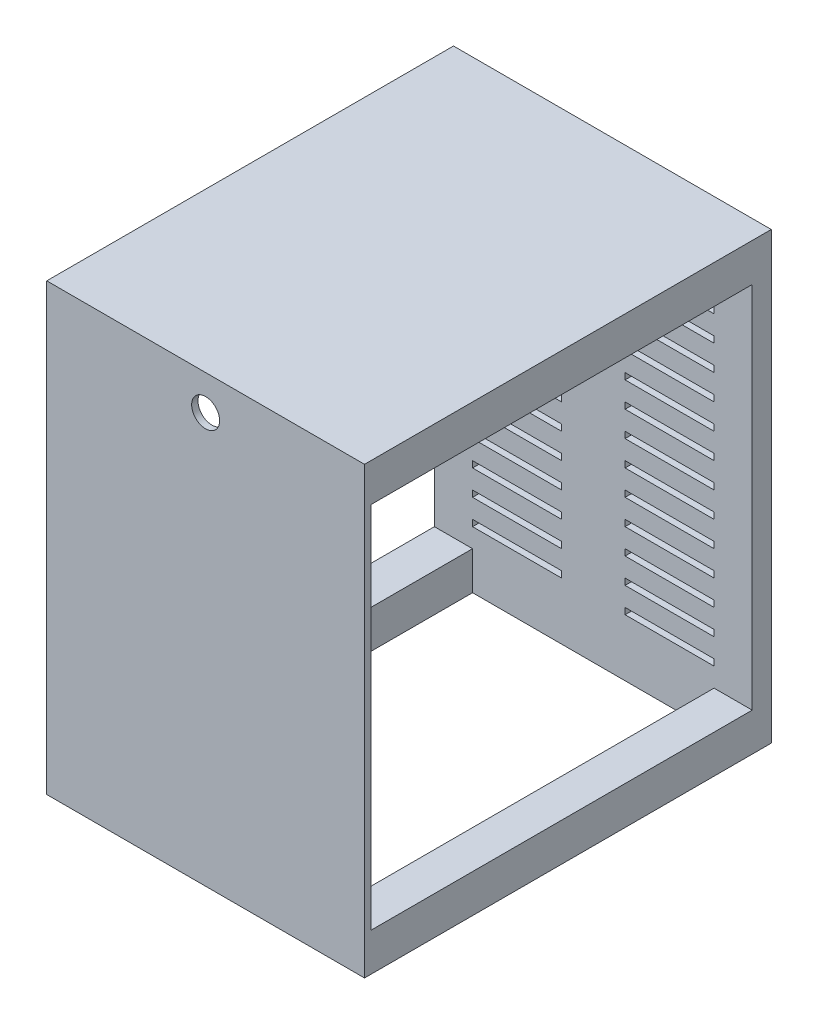
SolidWorks part; units mm, degrees
ref_plane "Alzado" through (0, 0, 0) normal (0, 0, 1) x (1, 0, 0)
ref_plane "Planta" through (0, 0, 0) normal (0, 1, 0) x (1, 0, 0)
ref_plane "Vista lateral" through (0, 0, 0) normal (1, 0, 0) x (0, 0, -1)
sketch "Croquis1" plane through (0, 0, 0) normal (0, 0, 1) x (1, 0, 0)
  line L1 (-125, -175) -> (125, -175)
  line L2 (-125, -175) -> (-125, 175)
  line L3 (-125, 175) -> (125, 175)
  line L4 (125, -175) -> (125, 175)
  line L5 (-125, -175) -> (125, 175) construction
  line L6 (-125, 175) -> (125, -175) construction
  point P0 (0, 0)
  dimension "D1" = 250
  dimension "D2" = 350
extrude "Saliente-Extruir2" add sketch "Croquis1" along normal blind 15 contours L3 L4 L1 L2
sketch "Croquis2" plane through (0, 0, 15) normal (0, 0, 1) x (1, 0, 0)
  line L1 (-125, 175) -> (-95, 175)
  line L2 (-125, 175) -> (-125, 145)
  line L3 (-125, 145) -> (-95, 145)
  line L4 (-95, 175) -> (-95, 145)
  line L5 (125, 175) -> (95, 175)
  line L6 (125, 175) -> (125, 145)
  line L7 (125, 145) -> (95, 145)
  line L8 (95, 175) -> (95, 145)
  line L9 (-125, -175) -> (-95, -175)
  line L10 (-125, -175) -> (-125, -145)
  line L11 (-125, -145) -> (-95, -145)
  line L12 (-95, -175) -> (-95, -145)
  line L13 (125, -175) -> (95, -175)
  line L14 (125, -175) -> (125, -145)
  line L15 (125, -145) -> (95, -145)
  line L16 (95, -175) -> (95, -145)
  dimension "D1" = 30
  dimension "D2" = 30
extrude "Saliente-Extruir3" add sketch "Croquis2" along normal blind 300
sketch "Croquis3" plane through (0, 0, 315) normal (0, 0, 1) x (1, 0, 0)
  line L1 (-125, 175) -> (125, 175)
  line L2 (-125, 175) -> (-125, -175)
  line L3 (-125, -175) -> (125, -175)
  line L4 (125, 175) -> (125, -175)
extrude "Saliente-Extruir4" add sketch "Croquis3" along normal blind 5
sketch "Croquis7" plane through (0, 0, 0) normal (0, 0, -1) x (-1, 0, 0)
  line L0 (25, 135) -> (95, 135)
  line L1 (-95, 135) -> (-25, 135)
  line L2 (-95, 135) -> (-95, 130)
  line L3 (-95, 130) -> (-25, 130)
  line L4 (-25, 135) -> (-25, 130)
  line L5 (95, 135) -> (95, 130)
  line L6 (25, 130) -> (95, 130)
  line L7 (25, 135) -> (25, 130)
  line L8 (25, 115) -> (95, 115)
  line L9 (95, 115) -> (95, 110)
  line L10 (25, 110) -> (95, 110)
  line L11 (25, 115) -> (25, 110)
  line L12 (25, 95) -> (95, 95)
  line L13 (95, 95) -> (95, 90)
  line L14 (25, 90) -> (95, 90)
  line L15 (25, 95) -> (25, 90)
  line L16 (25, 75) -> (95, 75)
  line L17 (95, 75) -> (95, 70)
  line L18 (25, 70) -> (95, 70)
  line L19 (25, 75) -> (25, 70)
  line L20 (25, 55) -> (95, 55)
  line L21 (95, 55) -> (95, 50)
  line L22 (25, 50) -> (95, 50)
  line L23 (25, 55) -> (25, 50)
  line L24 (25, 35) -> (95, 35)
  line L25 (95, 35) -> (95, 30)
  line L26 (25, 30) -> (95, 30)
  line L27 (25, 35) -> (25, 30)
  line L28 (25, 15) -> (95, 15)
  line L29 (95, 15) -> (95, 10)
  line L30 (25, 10) -> (95, 10)
  line L31 (25, 15) -> (25, 10)
  line L32 (25, -5) -> (95, -5)
  line L33 (95, -5) -> (95, -10)
  line L34 (25, -10) -> (95, -10)
  line L35 (25, -5) -> (25, -10)
  line L36 (25, -25) -> (95, -25)
  line L37 (95, -25) -> (95, -30)
  line L38 (25, -30) -> (95, -30)
  line L39 (25, -25) -> (25, -30)
  line L40 (25, -45) -> (95, -45)
  line L41 (95, -45) -> (95, -50)
  line L42 (25, -50) -> (95, -50)
  line L43 (25, -45) -> (25, -50)
  line L64 (-95, 115) -> (-25, 115)
  line L65 (-25, 115) -> (-25, 110)
  line L66 (-95, 110) -> (-25, 110)
  line L67 (-95, 115) -> (-95, 110)
  line L68 (-95, 95) -> (-25, 95)
  line L69 (-25, 95) -> (-25, 90)
  line L70 (-95, 90) -> (-25, 90)
  line L71 (-95, 95) -> (-95, 90)
  line L72 (-95, 75) -> (-25, 75)
  line L73 (-25, 75) -> (-25, 70)
  line L74 (-95, 70) -> (-25, 70)
  line L75 (-95, 75) -> (-95, 70)
  line L76 (-95, 55) -> (-25, 55)
  line L77 (-25, 55) -> (-25, 50)
  line L78 (-95, 50) -> (-25, 50)
  line L79 (-95, 55) -> (-95, 50)
  line L80 (-95, 35) -> (-25, 35)
  line L81 (-25, 35) -> (-25, 30)
  line L82 (-95, 30) -> (-25, 30)
  line L83 (-95, 35) -> (-95, 30)
  line L84 (-95, 15) -> (-25, 15)
  line L85 (-25, 15) -> (-25, 10)
  line L86 (-95, 10) -> (-25, 10)
  line L87 (-95, 15) -> (-95, 10)
  line L88 (-95, -5) -> (-25, -5)
  line L89 (-25, -5) -> (-25, -10)
  line L90 (-95, -10) -> (-25, -10)
  line L91 (-95, -5) -> (-95, -10)
  line L92 (-95, -25) -> (-25, -25)
  line L93 (-25, -25) -> (-25, -30)
  line L94 (-95, -30) -> (-25, -30)
  line L95 (-95, -25) -> (-95, -30)
  line L96 (-95, -45) -> (-25, -45)
  line L97 (-25, -45) -> (-25, -50)
  line L98 (-95, -50) -> (-25, -50)
  line L99 (-95, -45) -> (-95, -50)
  line L120 (-95, -65) -> (-25, -65)
  line L121 (-25, -65) -> (-25, -70)
  line L122 (-95, -70) -> (-25, -70)
  line L123 (-95, -65) -> (-95, -70)
  line L124 (25, -65) -> (95, -65)
  line L125 (95, -65) -> (95, -70)
  line L126 (25, -70) -> (95, -70)
  line L127 (25, -65) -> (25, -70)
  line L128 (-95, -85) -> (-25, -85)
  line L129 (-25, -85) -> (-25, -90)
  line L130 (-95, -90) -> (-25, -90)
  line L131 (-95, -85) -> (-95, -90)
  line L132 (25, -85) -> (95, -85)
  line L133 (95, -85) -> (95, -90)
  line L134 (25, -90) -> (95, -90)
  line L135 (25, -85) -> (25, -90)
  line L136 (-95, -105) -> (-25, -105)
  line L137 (-25, -105) -> (-25, -110)
  line L138 (-95, -110) -> (-25, -110)
  line L139 (-95, -105) -> (-95, -110)
  line L140 (25, -105) -> (95, -105)
  line L141 (95, -105) -> (95, -110)
  line L142 (25, -110) -> (95, -110)
  line L143 (25, -105) -> (25, -110)
  line L144 (-95, -125) -> (-25, -125)
  line L145 (-25, -125) -> (-25, -130)
  line L146 (-95, -130) -> (-25, -130)
  line L147 (-95, -125) -> (-95, -130)
  line L148 (25, -125) -> (95, -125)
  line L149 (95, -125) -> (95, -130)
  line L150 (25, -130) -> (95, -130)
  line L151 (25, -125) -> (25, -130)
  line L152 (-95, 135) -> (-95, 175) construction
  line L153 (125, 175) -> (-125, 175) construction
  line L154 (-95, 135) -> (-125, 135) construction
  line L155 (-125, -175) -> (-125, 175) construction
  line L156 (-95, 130) -> (-125, 130) construction
  line L157 (95, 135) -> (125, 135) construction
  line L158 (125, -175) -> (125, 175) construction
  dimension "D1" = 5
  dimension "D2" = 70
  dimension "D5" = 40
  dimension "D3" = 2
  dimension "D4" = 14
extrude "Cortar-Extruir1" cut sketch "Croquis7" against normal blind 20
sketch "Croquis9" plane through (0, 175, 0) normal (0, 1, 0) x (1, 0, 0)
  line L1 (125, -320) -> (-125, -320)
  line L2 (125, -320) -> (125, 0)
  line L3 (125, 0) -> (-125, 0)
  line L4 (-125, -320) -> (-125, 0)
extrude "Saliente-Extruir6" add sketch "Croquis9" against normal blind 5
sketch "Croquis11" plane through (0, 0, 320) normal (0, 0, 1) x (1, 0, 0)
  circle A0 centre (0, 147.6644) radius 11
  dimension "D1" = 22
extrude "Cortar-Extruir3" cut sketch "Croquis11" against normal blind 10
